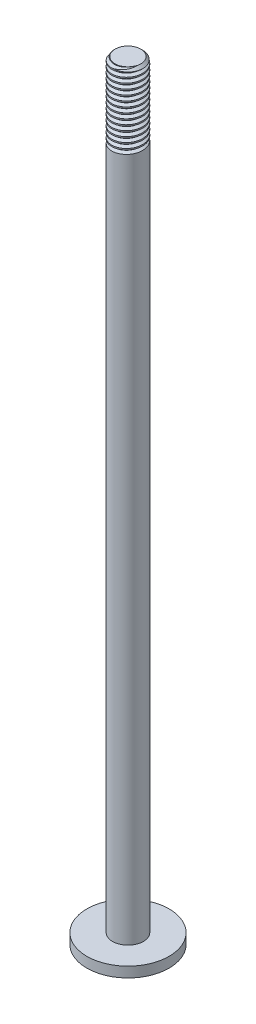
SolidWorks part; units mm, degrees
material "6063-T5"
ref_plane "Plano frontal" through (0, 0, 0) normal (0, 0, 1) x (1, 0, 0)
ref_plane "Plano superior" through (0, 0, 0) normal (0, 1, 0) x (1, 0, 0)
ref_plane "Plano direito" through (0, 0, 0) normal (1, 0, 0) x (0, 0, -1)
sketch "Esboço1" plane through (0, 0, 0) normal (0, 1, 0) x (1, 0, 0)
  circle A0 centre (0, 0) radius 8
  dimension "D1" = 16
extrude "Ressalto-extrusão1" add sketch "Esboço1" along normal blind 2
sketch "Esboço2" plane through (0, 2, 0) normal (0, 1, 0) x (1, 0, 0)
  circle A0 centre (0, 0) radius 3
  dimension "D1" = 6
extrude "Ressalto-extrusão2" add sketch "Esboço2" along normal blind 147.6
chamfer "Chanfro1" distance 0.5 angle 45 1 edges at (0, 149.6, 3)
thread "Rosca1" pitch 1 method cut trim with start face yes profile "Perfil da rosca1" start angle 0, offset 1, length 15, pitch 1, diameter 6
ref_plane "Plano1" through (-3, 150.6, 0) normal (0, 0, -1) x (1, 0, 0)
sketch "Perfil da rosca1" plane through (-3, 150.6, 0) normal (0, 0, -1) x (1, 0, 0)
  line L0 (0, 0) -> (0, 1) construction
  line L1 (0, 0) -> (0.5413, 0.3125)
  line L2 (0.5413, 0.3125) -> (0.5413, 0.4375)
  line L3 (0.5413, 0.4375) -> (0, 0.75)
  line L4 (0.5413, 0.375) -> (0, 0.375) construction
  line L11 (0, 0) -> (0, 0.75)
  point P2 (0, 0)
  dimension "Pitch" = 1
  dimension "Profile_Angle" = 60
  dimension "Profile_Land" = 0.125
  dimension "Profile_Height" = 0.5413
